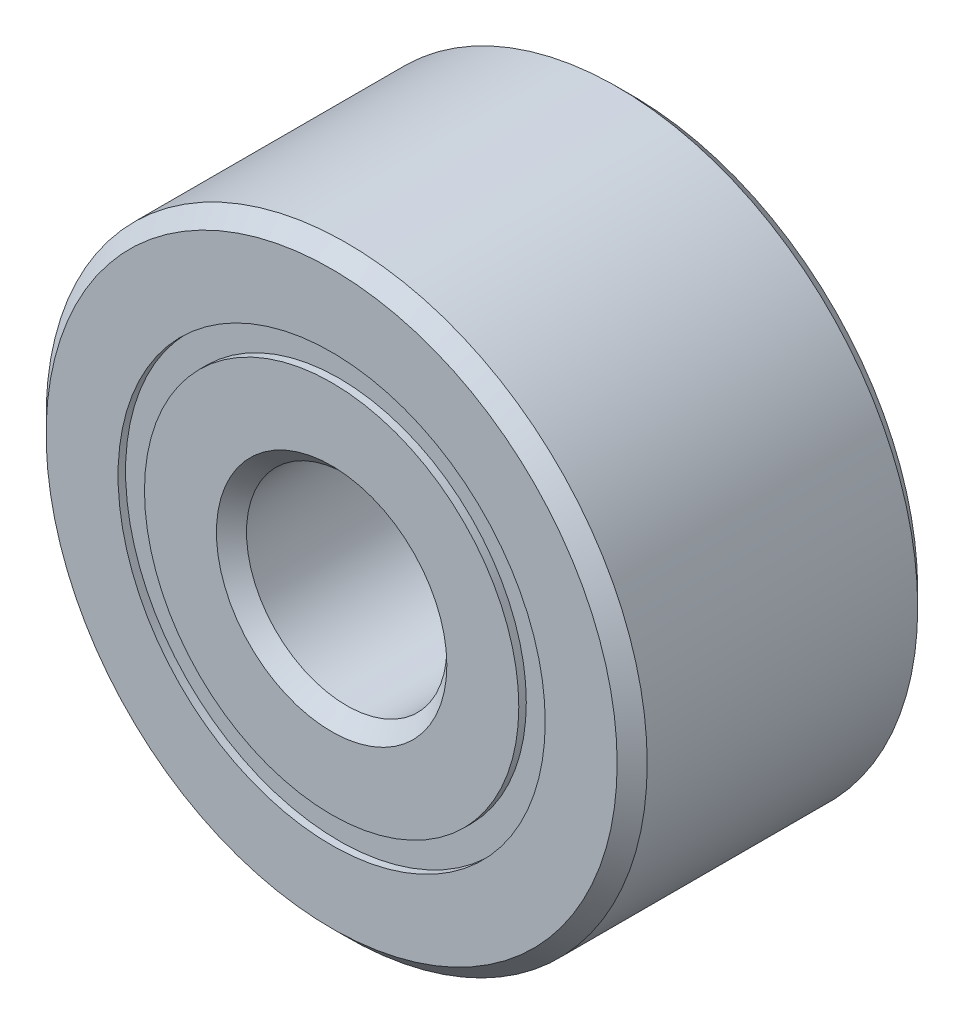
SolidWorks part; units mm, degrees
material "Cast Alloy Steel"
ref_plane "Front Plane" through (0, 0, 0) normal (0, 0, 1) x (1, 0, 0)
ref_plane "Top Plane" through (0, 0, 0) normal (0, 1, 0) x (1, 0, 0)
ref_plane "Right Plane" through (0, 0, 0) normal (1, 0, 0) x (0, 0, -1)
sketch "Sketch1" plane through (0, 0, 0) normal (1, 0, 0) x (0, 0, -1)
  line L0 (-1.5, 0) -> (1.5, 0) construction
  line L1 (0, 3) -> (0, -3) construction
  line L2 (1.35, 3) -> (-1.35, 3)
  line L3 (-1.35, 3) -> (-1.5, 2.85)
  line L4 (-1.5, 2.85) -> (-1.5, 2.1319)
  line L5 (-1.5, 2.1319) -> (-0.6667, 2.1319)
  line L6 (1.5, 2.1319) -> (0.6667, 2.1319)
  line L7 (1.5, 2.85) -> (1.5, 2.1319)
  line L8 (1.35, 3) -> (1.5, 2.85)
  line L9 (0, 3) -> (0, 2) construction
  line L10 (0, 2) -> (0, 1) construction
  arc A0 (-0.6667, 2.1319) -> (0.6667, 2.1319) centre (0, 2) cw
  point P14 (0, 1)
  dimension "Width" = 3
  dimension "OD" = 6
  dimension "D1" = 45
  dimension "D2" = 0.15
  dimension "Shaft Dia" = 2
  dimension "D3" = 1.3333
  dimension "D4" = 0.1319
revolve "Revolve1" add sketch "Sketch1" angle 360 about L0
sketch "Sketch3" plane through (0, 0, 0) normal (1, 0, 0) x (0, 0, -1)
  line L0 (-1.5, 1.8681) -> (-0.6667, 1.8681)
  line L1 (0, 3) -> (0, -3) construction
  line L2 (-1.5, 2.85) -> (-1.5, 2.1319) construction
  line L3 (-1.5, 1.8681) -> (-1.5, 1.15)
  line L4 (-1.35, 3) -> (-1.5, 2.85) construction
  line L5 (-1.5, 1.15) -> (-1.35, 1)
  line L6 (-1.35, 1) -> (1.35, 1)
  line L7 (1.35, 3) -> (1.35, -3) construction
  line L8 (1.35, 1) -> (1.5, 1.15)
  line L9 (1.5, -2.85) -> (1.5, 2.85) construction
  line L10 (1.5, 1.15) -> (1.5, 1.8681)
  line L11 (1.5, 1.8681) -> (0.6667, 1.8681)
  line L13 (1.35, 3) -> (1.5, 2.85) construction
  arc A0 (0.6667, 2.1319) -> (-0.6667, 2.1319) centre (0, 2) ccw construction
  arc A1 (0.6667, 1.8681) -> (-0.6667, 1.8681) centre (0, 2) cw
revolve "Revolve3" add sketch "Sketch3" angle 360 about L0
sketch "Sketch4" plane through (0, 0, 0) normal (1, 0, 0) x (0, 0, -1)
  line L0 (-0.6796, 2) -> (0.6796, 2)
  arc A2 (-0.6796, 2) -> (0.6796, 2) centre (0, 2) cw
  arc A3 (0.6667, 2.1319) -> (-0.6667, 2.1319) centre (0, 2) ccw construction
revolve "Revolve4" add sketch "Sketch4" angle 360 about L0
ref_axis "Axis1" through (0, 0, -1.5) along (0, 0, 1)
pattern_circular "CirPattern1" count 12 every 30 about axis through (0, 0, -1.5) along (0, 0, 1) of bodies 104
sketch "Sketch5" plane through (0, 0, 0) normal (1, 0, 0) x (0, 0, -1)
  line L0 (-1.5, 2.1319) -> (-0.6667, 2.1319) construction
  line L1 (-1.425, 2.1319) -> (-0.6796, 2.1319)
  line L2 (-1.425, 2.1319) -> (-1.425, 1.8681)
  line L3 (-1.425, 1.8681) -> (-0.6796, 1.8681)
  line L4 (-0.6796, 2.1319) -> (-0.6796, 1.8681)
  line L5 (-1.5, 1.8681) -> (-0.6667, 1.8681) construction
  line L6 (1.5, 2.1319) -> (0.6667, 2.1319) construction
  line L7 (1.425, 2.1319) -> (0.6796, 2.1319)
  line L8 (1.425, 2.1319) -> (1.425, 1.8681)
  line L9 (1.425, 1.8681) -> (0.6796, 1.8681)
  line L10 (0.6796, 2.1319) -> (0.6796, 1.8681)
  line L11 (1.5, 1.8681) -> (0.6667, 1.8681) construction
  line L12 (-1.35, 3) -> (-1.5, 2.85) construction
  point P18 (-1.425, 2.925)
revolve "Revolve5" add sketch "Sketch5" angle 360 about L0
sketch "Sketch6" plane through (0, 0, 0) normal (1, 0, 0) x (0, 0, -1)
  line L0 (1.5, 0) -> (-1.5, 0) construction
  line L1 (1.5, 2.1319) -> (0.7126, 2.1319)
  line L2 (1.5, 2.1319) -> (1.5, 6.9469)
  line L3 (1.5, 6.9469) -> (0.7126, 6.9469)
  line L4 (0.7126, 2.1319) -> (0.7126, 6.9469)
  dimension "Th" = 0.7874
  dimension "Flange OD" = 13.8938
revolve "Revolve6" [suppressed] add sketch "Sketch6" angle 360 about L0
equation "\"D2@Sketch1\" = \"Width@Sketch1\"*.05"
equation "\"D3@Sketch1\" = \"Width@Sketch1\"/2.25"
equation "\"D4@Sketch1\" = (((\"OD@Sketch1\"-\"Width@Sketch1\")/2)/3.25)/3.5"
equation "\"D2@CirPattern1\" = 360/\"Balls@CirPattern1\""
